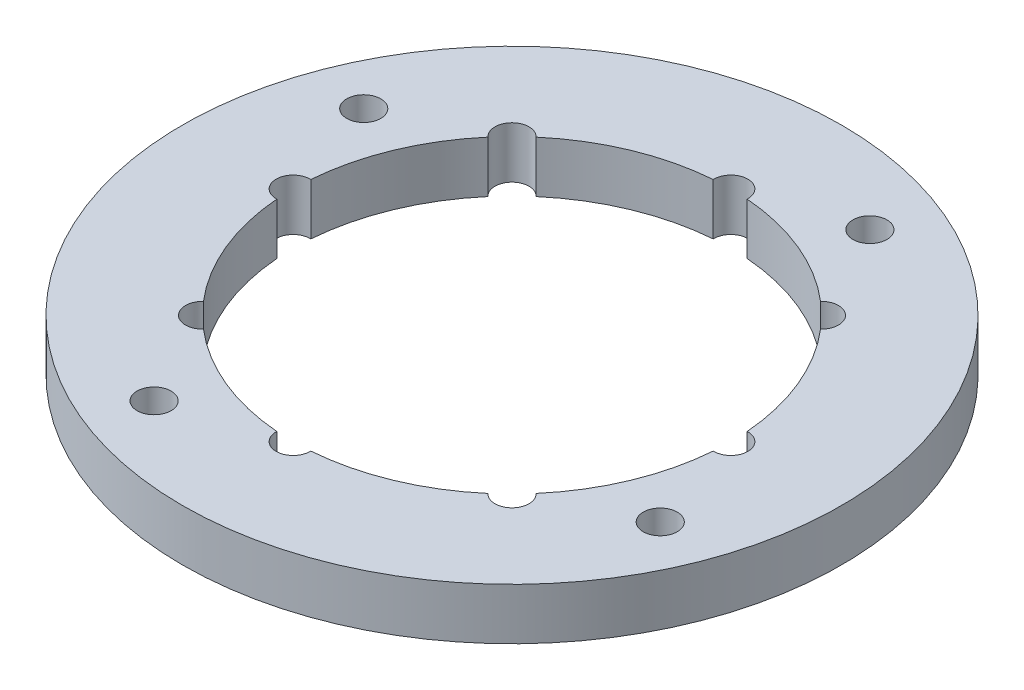
SolidWorks part; units mm, degrees
ref_plane "Front Plane" through (0, 0, 0) normal (0, 0, 1) x (1, 0, 0)
ref_plane "Top Plane" through (0, 0, 0) normal (0, 1, 0) x (1, 0, 0)
ref_plane "Right Plane" through (0, 0, 0) normal (1, 0, 0) x (0, 0, -1)
sketch "1.5in Socket" plane through (0, 0, 0) normal (0, 1, 0) x (1, 0, 0)
  line L0 (0, 0) -> (-19.083, 19.083) construction
  line L1 (0, 26.9875) -> (0, 0)
  line L2 (19.083, 19.083) -> (0, 0) construction
  line L3 (26.9875, 0) -> (0, 0)
  line L4 (19.083, -19.083) -> (0, 0) construction
  line L5 (0, -26.9875) -> (0, 0)
  line L6 (-19.083, -19.083) -> (0, 0) construction
  line L7 (-26.9875, 0) -> (0, 0) construction
  line L8 (-12.9278, -31.2105) -> (0, 0) construction
  line L9 (-31.2105, 12.9278) -> (0, 0) construction
  line L10 (31.2105, -12.9278) -> (0, 0) construction
  line L11 (12.9278, 31.2105) -> (0, 0) construction
  circle A0 centre (0, 0) radius 40.64
  arc A1 (-2.0939, 26.9061) -> (2.0939, 26.9061) centre (0, 26.9875) cw
  arc A2 (2.0939, 26.9061) -> (17.5449, 20.5061) centre (0, 0) cw
  arc A3 (17.5449, 20.5061) -> (20.5061, 17.5449) centre (19.083, 19.083) cw
  arc A4 (20.5061, 17.5449) -> (26.9061, 2.0939) centre (0, 0) cw
  arc A5 (26.9061, 2.0939) -> (26.9061, -2.0939) centre (26.9875, 0) cw
  arc A6 (26.9061, -2.0939) -> (20.5061, -17.5449) centre (0, 0) cw
  arc A7 (20.5061, -17.5449) -> (17.5449, -20.5061) centre (19.083, -19.083) cw
  arc A8 (17.5449, -20.5061) -> (2.0939, -26.9061) centre (0, 0) cw
  arc A9 (2.0939, -26.9061) -> (-2.0939, -26.9061) centre (0, -26.9875) cw
  arc A10 (-2.0939, -26.9061) -> (-17.5449, -20.5061) centre (0, 0) cw
  arc A11 (-17.5449, -20.5061) -> (-20.5061, -17.5449) centre (-19.083, -19.083) cw
  arc A12 (-20.5061, -17.5449) -> (-26.9061, -2.0939) centre (0, 0) cw
  arc A13 (-26.9061, -2.0939) -> (-26.9061, 2.0939) centre (-26.9875, 0) cw
  arc A14 (-26.9061, 2.0939) -> (-20.5061, 17.5449) centre (0, 0) cw
  arc A15 (-20.5061, 17.5449) -> (-17.5449, 20.5061) centre (-19.083, 19.083) cw
  arc A16 (-17.5449, 20.5061) -> (-2.0939, 26.9061) centre (0, 0) cw
  arc A18 (-2.0939, 26.9061) -> (-17.5449, 20.5061) centre (0, 0) ccw
  arc A19 (-17.5449, 20.5061) -> (-20.5061, 17.5449) centre (-19.083, 19.083) ccw
  arc A20 (-20.5061, 17.5449) -> (-26.9061, 2.0939) centre (0, 0) ccw
  arc A21 (-26.9061, 2.0939) -> (-26.9061, -2.0939) centre (-26.9875, 0) ccw
  arc A22 (-26.9061, -2.0939) -> (-20.5061, -17.5449) centre (0, 0) ccw
  arc A23 (-20.5061, -17.5449) -> (-17.5449, -20.5061) centre (-19.083, -19.083) ccw
  arc A24 (-17.5449, -20.5061) -> (-2.0939, -26.9061) centre (0, 0) ccw
  arc A25 (-2.0939, -26.9061) -> (2.0939, -26.9061) centre (0, -26.9875) ccw
  arc A26 (2.0939, -26.9061) -> (17.5449, -20.5061) centre (0, 0) ccw
  arc A27 (17.5449, -20.5061) -> (20.5061, -17.5449) centre (19.083, -19.083) ccw
  arc A28 (20.5061, -17.5449) -> (26.9061, -2.0939) centre (0, 0) ccw
  arc A29 (26.9061, -2.0939) -> (26.9061, 2.0939) centre (26.9875, 0) ccw
  arc A30 (26.9061, 2.0939) -> (20.5061, 17.5449) centre (0, 0) ccw
  arc A31 (20.5061, 17.5449) -> (17.5449, 20.5061) centre (19.083, 19.083) ccw
  arc A32 (17.5449, 20.5061) -> (2.0939, 26.9061) centre (0, 0) ccw
  arc A33 (2.0939, 26.9061) -> (-2.0939, 26.9061) centre (0, 26.9875) ccw
  circle A34 centre (-12.9278, -31.2105) radius 2.1
  circle A35 centre (-31.2105, 12.9278) radius 2.1
  circle A36 centre (31.2105, -12.9278) radius 2.1
  circle A37 centre (12.9278, 31.2105) radius 2.1
  point P27 (-19.083, -19.083)
  point P28 (-26.9875, 0)
  point P29 (0, 0)
  point P30 (0, -26.9875)
  point P31 (19.083, -19.083)
  point P32 (26.9875, 0)
  point P33 (19.083, 19.083)
  point P34 (0, 26.9875)
  point P35 (-19.083, 19.083)
  point P36 (0, 0)
  point P39 (47.4332, -12.4563)
  point P44 (0.7613, -0.7613)
  point P47 (0, 0)
  dimension "D1" = 2.0955
  dimension "D2" = 2.0955
  dimension "D3" = 2.0955
  dimension "D4" = 2.0955
  dimension "D5" = 2.0955
  dimension "D6" = 2.0955
  dimension "D7" = 2.0955
  dimension "D8" = 2.0955
  dimension "D9" = 26.9875
  dimension "D10" = 26.9875
  dimension "D11" = 26.9875
  dimension "D12" = 26.9875
  dimension "D13" = 26.9875
  dimension "D14" = 26.9875
  dimension "D15" = 26.9875
  dimension "D16" = 26.9875
  dimension "D17" = 81.28
  dimension "D26" = 4.2
  dimension "D28" = 33.782
  dimension "D30" = 4.2
  dimension "D31" = 4.2
  dimension "D32" = 4.2
  dimension "D18" = 26.9875
  dimension "D19" = 26.9875
  dimension "D20" = 26.9875
  dimension "D21" = 26.9875
  dimension "D22" = 26.9875
  dimension "D23" = 26.9875
  dimension "D24" = 26.9875
  dimension "D25" = 26.9875
  dimension "D27" = 33.782
  dimension "D29" = 90
  dimension "D33" = 90
  dimension "D34" = 90
  dimension "D35" = 33.782
  dimension "D36" = 33.782
  dimension "D37" = 67.5
extrude "Boss-Extrude1" add sketch "1.5in Socket" along normal blind 6.35 contours A0 A37 A36 A35 A34 A15 A16 A1 A2 A3 A4 A5 A6 A7 A8 A9 A10 A11 A12 A13 A14 region at (-39.4905, 0, 0)
